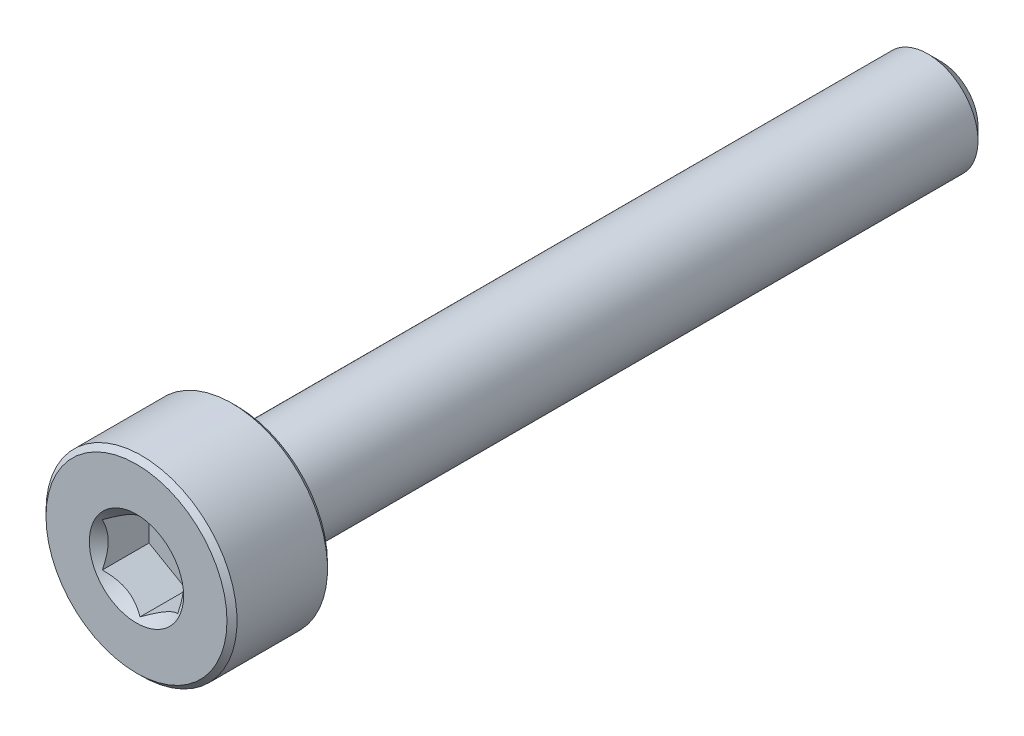
SolidWorks part; units mm, degrees
ref_plane "Front Plane" through (0, 0, 0) normal (0, 0, 1) x (1, 0, 0)
ref_plane "Top Plane" through (0, 0, 0) normal (0, 1, 0) x (1, 0, 0)
ref_plane "Right Plane" through (0, 0, 0) normal (1, 0, 0) x (0, 0, -1)
sketch "Sketch1" plane through (0, 0, 0) normal (1, 0, 0) x (0, 0, -1)
  line L0 (-8, 0) -> (8, 0) construction
  line L1 (8, 0) -> (8, 0.7402) construction
  line L2 (8, 0.7402) -> (7.7402, 1) construction
  line L3 (7.7402, 1) -> (7.7, 1) construction
  line L4 (7.7, 1) -> (-6, 1) construction
  line L5 (-6, 1) -> (-6, 1.9) construction
  line L6 (-6, 1.9) -> (-8, 1.9) construction
  line L7 (-8, 1.9) -> (-8, 0) construction
  line L8 (8, 0.7402) -> (8, 1) construction
  line L9 (7.975, 1.0433) -> (8.175, 0.6969) construction
  line L10 (8.175, 0.6969) -> (8.375, 1.0433) construction
  line L11 (8.375, 1.0433) -> (7.975, 1.0433) construction
  line L12 (8.175, 1.0433) -> (8.175, 1) construction
  line L13 (8.175, 0.6969) -> (8.175, 0.7402) construction
  line L14 (8.15, 0.7402) -> (8.2, 0.7402) construction
  line L15 (8, 1) -> (8.35, 1) construction
  line L16 (7.9875, 1.0217) -> (8.3625, 1.0217) construction
  line L17 (8, 0) -> (8, -1) construction
  line L18 (-6.1, 1.9) -> (-6, 1.8) construction
  line L19 (-7.9, 1.9) -> (-8, 1.8) construction
  line L20 (-6, 1) -> (-6, 0) construction
  line L21 (-6, 0.5) -> (-1.3333, 0.5) construction
  line L22 (-1.3333, 0.5) -> (3.3333, 0.5) construction
  line L23 (3.3333, 0.5) -> (8, 0.5) construction
  line L24 (-1.3333, 0.5) -> (-1.3333, 1) construction
  line L25 (-1.3333, 1) -> (-1.3333, 1.9) construction
  line L26 (3.3333, 0.5) -> (3.3333, 1.9) construction
  point P0 (-8, 0.75)
  point P3 (7, 1)
  point P4 (0, 0)
  point P18 (3.3333, 1)
  point P22 (8.175, 0.7402)
  point P24 (7.7, 1)
  point P25 (8.175, 1)
  point P28 (8.175, 1.0217)
  point P29 (7, -1)
  point P30 (-1.3333, 1)
  point P31 (-7, 1.9)
  point P37 (-6.35, 1.9)
  point P38 (-7.85, 1.9)
  point P45 (-1.3333, 0.5)
  point P46 (3.3333, 0.5)
  dimension "D2" = 0.05
  dimension "D7" = 0.1
  dimension "D8" = 0.1
  dimension "D9" = 0.1
  dimension "D10" = 0.05
  dimension "D11" = 0.25
  dimension "Drive Size" = 1.5
  dimension "Head Diameter" = 3.8
  dimension "Head Height" = 2
  dimension "Thread Pitch" = 0.4
  dimension "Thread Size" = 2
  dimension "Length" = 14
  dimension "D12" = 0.3
  dimension "D4" = 1
  dimension "D3" = 45
sketch "Sketch2" plane through (0, 0, 0) normal (1, 0, 0) x (0, 0, -1)
  line L0 (-8, 0) -> (-8, 1.8)
  line L1 (-7.9, 1.9) -> (-6.1, 1.9)
  line L2 (-6, 1.8) -> (-6, 1.2)
  line L4 (7.7402, 1) -> (8, 0.7402)
  line L5 (8, 0.7402) -> (8, 0)
  line L6 (-6, 1.9) -> (-8, 1.9) construction
  line L7 (8, 0) -> (-8, 0)
  line L8 (-7.9, 1.9) -> (-8, 1.8) construction
  line L10 (-7.9, 1.9) -> (-8, 1.8)
  line L14 (-6.1, 1.9) -> (-6, 1.8) construction
  line L16 (-6.1, 1.9) -> (-6, 1.8)
  line L17 (-6, 1) -> (-6, 1.9) construction
  line L19 (-5.8, 1) -> (7.7402, 1)
  line L20 (7.7, 1) -> (-6, 1) construction
  arc A1 (-6, 1.2) -> (-5.8, 1) centre (-5.8, 1.2) ccw
  dimension "D3" = 0.2
revolve "Revolve1" add sketch "Sketch2" angle 360 about L7
sketch "Sketch3" plane through (0, 0, 8) normal (0, 0, 1) x (1, 0, 0)
  line L1 (0.75, -0.433) -> (0.75, 0.433)
  line L2 (0.75, 0.433) -> (0, 0.866)
  line L3 (0, 0.866) -> (-0.75, 0.433)
  line L4 (-0.75, 0.433) -> (-0.75, -0.433)
  line L5 (-0.75, -0.433) -> (0, -0.866)
  line L6 (0, -0.866) -> (0.75, -0.433)
  circle A0 centre (0, 0) radius 0.75 construction
  circle A1 centre (0, 0) radius 1.9 construction
  circle A2 centre (0, 0) radius 1.9 construction
  circle A3 centre (0, 0) radius 0.866 construction
  point P13 (0, 0)
extrude "Cut-Extrude1" cut sketch "Sketch3" against normal offset from surface (1 mm away) 1 up to face at (-1.8, 0, 6)
sketch "Sketch4" plane through (0, 0, 8) normal (0, 0, 1) x (1, 0, 0)
  circle A0 centre (0, 0) radius 0.9375
  dimension "D1" = 1.875
extrude "Cut-Extrude2" cut sketch "Sketch4" against normal up to vertex (1 mm away) draft 45 up to point (0, 1.9, 7)
sketch "Sketch11" plane through (0, 0, 0) normal (1, 0, 0) x (0, 0, -1)
  line L0 (-8, 0) -> (8, 0) construction
  line L1 (-8, 0) -> (8, 0) construction
  line L2 (-3.375, 0) -> (-3.375, 1) construction
  line L3 (7.7, 1) -> (-6, 1) construction
  line L4 (5.375, 0) -> (5.375, 1) construction
  line L6 (8, 0.7402) -> (8, 1) construction
  point P2 (-3.375, 0)
  point P3 (5.375, 0)
  dimension "D1" = 2.625
  dimension "D2" = 2.625
sketch "Sketch6" [suppressed] plane through (0, 0, -8) normal (0, 0, -1) x (-1, 0, 0)
  circle A0 centre (0, 0) radius 1
curve "Helix/Spiral1" [suppressed] pitch 0.4 height 14.4 turns 36
sketch "Sketch10" [suppressed] plane through (0, 0, 0) normal (1, 0, 0) x (0, 0, -1)
  line L0 (-5.8, -1.9) -> (-5.8, 1.9)
  line L5 (-8, 0) -> (8, 0) construction
  line L6 (-5.8, 1) -> (-5.8, -1) construction
  point P3 (-5.8, 0)
split "Split1" [suppressed] bodies to split 106
sketch "Sketch7" [suppressed] plane through (0, 0, 0) normal (1, 0, 0) x (0, 0, -1)
  line L0 (7.9875, 1.0217) -> (8.3625, 1.0217)
  line L1 (8.3625, 1.0217) -> (8.2, 0.7402)
  line L2 (8.2, 0.7402) -> (8.15, 0.7402)
  line L3 (8.15, 0.7402) -> (7.9875, 1.0217)
sweep "Cut-Sweep1" [suppressed] cut profiles "Sketch7" path "Helix/Spiral1"
sketch "Sketch8" [suppressed] plane through (0, 0, 0) normal (1, 0, 0) x (0, 0, -1)
  line L0 (-6, 0) -> (-6, 1)
  line L1 (-5.8, -1) -> (-5.8, 1) construction
  line L2 (-6, 1) -> (-5.8, 1)
  line L4 (-5.8, 1) -> (-5.2226, 0)
  line L5 (-5.2226, 0) -> (-6, 0)
  line L6 (7.7, 1) -> (-6, 1) construction
  line L7 (-8, 0) -> (8, 0) construction
  dimension "D1" = 60
revolve "Revolve2" [suppressed] add sketch "Sketch8" angle 360 about L5
equation "\"D2@Sketch1\" = \"Thread Pitch@Sketch1\" / 8"
equation "\"D4@Helix/Spiral1\" = \"Thread Pitch@Sketch1\""
equation "\"D7@Sketch1\" = \"Head Height@Sketch1\" * .05"
equation "\"D8@Sketch1\"=\"D7@Sketch1\""
equation "\"D9@Sketch1\"=\"D7@Sketch1\""
equation "\"D10@Sketch1\"=\"D7@Sketch1\"/2"
equation "\"D11@Sketch1\"=\"D10@Sketch1\"*5"
equation "\"D4@Sketch1\"=\"Thread Pitch@Sketch1\"*2.5"
equation "\"D12@Sketch1\"=\"Thread Pitch@Sketch1\"*.75"
equation "\"D3@Helix/Spiral1\"=\"Length@Sketch1\"+\"Thread Pitch@Sketch1\""
equation "\"D1@Sketch11\"=\"Length@Sketch1\"*0.1875"
equation "\"D2@Sketch11\"=\"D1@Sketch11\""
equation "\"D1@Sketch4\"=\"Drive Size@Sketch1\"*1.25"
